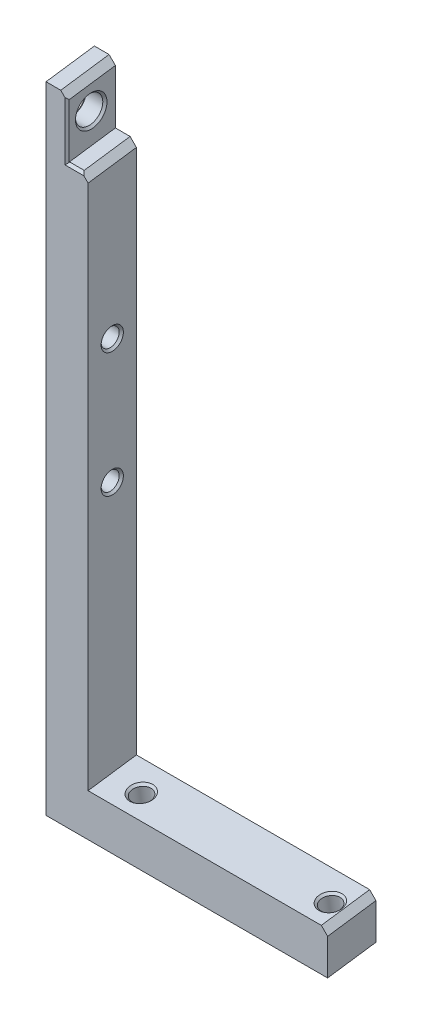
SolidWorks part; units mm, degrees
ref_plane "Top" through (0, 0, 0) normal (0, 0, 1) x (1, 0, 0)
ref_plane "Front" through (0, 0, 0) normal (0, 1, 0) x (1, 0, 0)
ref_plane "Right" through (0, 0, 0) normal (1, 0, 0) x (0, 0, -1)
sketch "Sketch4" plane through (0, 0, 0) normal (1, 0, 0) x (0, 0, -1)
  line L1 (0, 0) -> (11.5, 0)
  line L2 (0, 0) -> (0, 144)
  line L3 (0, 144) -> (11.5, 144)
  line L4 (11.5, 0) -> (11.5, 144)
  dimension "D1" = 11.5
  dimension "D2" = 144
extrude "Boss-Extrude2" add sketch "Sketch4" along normal blind 10
sketch "Sketch6" plane through (10, 0, 0) normal (1, 0, 0) x (0, 0, -1)
  line L0 (5.75, 0) -> (11.5, 0.8081)
  line L1 (0, 0) -> (11.5, 0) construction
  line L2 (11.5, 0) -> (11.5, 144) construction
  line L3 (11.5, 0.8081) -> (10.1083, 10.7108)
  line L4 (10.1083, 10.7108) -> (0.2056, 9.3191)
  line L5 (0.2056, 9.3191) -> (1.5973, -0.5836)
  line L6 (1.5973, -0.5836) -> (5.75, 0)
  line L7 (0, 144) -> (0, 0) construction
  dimension "D1" = 10
  dimension "D2" = 10
  dimension "D3" = 82
extrude "Boss-Extrude3" add sketch "Sketch6" along normal blind 57 and the other way blind 10
sketch "Sketch7" plane through (10, 0, 0) normal (1, 0, 0) x (0, 0, -1)
  line L0 (-3.1126, -1.2456) -> (11.8209, -3.029)
  line L2 (11.8209, -3.029) -> (11.8209, 0.8532)
  line L3 (11.8209, 0.8532) -> (-3.1126, -1.2456)
  line L4 (1.5973, -0.5836) -> (11.5, 0.8081) construction
extrude "Cut-Extrude2" cut sketch "Sketch7" against normal blind 10
sketch "Sketch8" plane through (0, 9.1102, 1.2804) normal (0, 0.9903, 0.1392) x (1, 0, 0)
  line L0 (10, 1.5005) -> (67, 1.5005) construction
  line L1 (67, 11.5005) -> (67, 1.5005) construction
  circle A0 centre (62.5, 6.5005) radius 2.25
  circle A1 centre (17.5, 6.5005) radius 2.25
  dimension "D2" = 4.5
  dimension "D3" = 4.5
  dimension "D1" = 45
  dimension "D4" = 5
  dimension "D5" = 4.5
extrude "Cut-Extrude3" cut sketch "Sketch8" against normal blind 10
sketch "Sketch11" plane through (0, 9.1102, 1.2804) normal (0, 0.9903, 0.1392) x (1, 0, 0)
  line L0 (13.5, 6.5005) -> (13.5, 0)
  line L1 (13.5, 0) -> (21.5, 0)
  line L3 (21.5, 0) -> (21.5, 6.5005)
  line L4 (10, 0) -> (0, 0) construction
  circle A0 centre (17.5, 6.5005) radius 4 construction
  arc A1 (21.5, 6.5005) -> (13.5, 6.5005) centre (17.5, 6.5005) ccw
  dimension "D1" = 8
sketch "Sketch12" plane through (67, 0, 0) normal (1, 0, 0) x (0, 0, -1)
  line L5 (0.2056, 9.3191) -> (10.1083, 10.7108) construction
  line L13 (1.5973, -0.5836) -> (0, -0.8081)
  line L14 (0, -0.8081) -> (0, 9.2902)
  line L16 (1.5973, -0.5836) -> (11.5, 0.8081) construction
  line L17 (0, 144) -> (0, 0) construction
  line L18 (11.5, 0.8081) -> (11.5, 10.9064)
  line L20 (11.5, 10.9064) -> (10.1083, 10.7108)
  line L21 (10.1083, 10.7108) -> (11.5, 0.8081)
  line L22 (10.1083, 10.7108) -> (0.2056, 9.3191) construction
  line L23 (11.5, 0.8081) -> (11.5, 144) construction
  line L25 (11.5, 0.8081) -> (10.1083, 10.7108) construction
  line L26 (0, 9.2902) -> (0.2056, 9.3191)
  line L27 (0.2056, 9.3191) -> (1.5973, -0.5836)
  line L28 (0.2056, 9.3191) -> (1.5973, -0.5836) construction
extrude "Boss-Extrude4" add sketch "Sketch12" against normal up to surface (67 mm away) up to face at (0, 48.0374, -4.3521)
sketch "Sketch13" plane through (10, 0, 0) normal (1, 0, 0) x (0, 0, -1)
  line L0 (11.5, 144) -> (11.5, 152)
  line L1 (11.5, 152) -> (0, 150.3838)
  line L2 (0, 150.3838) -> (0, 144)
  line L3 (0, 144) -> (11.5, 144)
  line L4 (11.5, 10.9064) -> (0, 9.2902) construction
  dimension "D1" = 8
extrude "Boss-Extrude5" add sketch "Sketch13" against normal blind 10
sketch "Sketch14" plane through (10, 0, 0) normal (1, 0, 0) x (0, 0, -1)
  line L0 (11.5, 10.9064) -> (11.5, 152) construction
  circle A0 centre (5.75, 144) radius 3.25
  dimension "D2" = 6.5
  dimension "D1" = 8
  dimension "D3" = 5.75
extrude "Cut-Extrude5" cut sketch "Sketch14" against normal blind 10
sketch "Sketch18" plane through (10, 0, 0) normal (1, 0, 0) x (0, 0, -1)
  line L0 (5.75, 99.6) -> (5.75, 70)
  line L1 (11.5, 10.9064) -> (11.5, 152) construction
  dimension "D1" = 5.75
  dimension "D2" = 29.6
  dimension "D3" = 70
hole_wizard "M4 Clearance Hole1" positions "Sketch19" profile "Sketch20" hole size "M4" standard "DIN" end condition through all
sketch "Sketch19" plane through (10, 0, 0) normal (1, 0, 0) x (0, 0, -1)
  point P0 (5.75, 70)
  point P3 (5.75, 99.6)
sketch "Sketch20" plane through (10, 70, -5.75) normal (0, 1, 0) x (0, 0, -1)
  line L0 (0, 0) -> (0, 10)
  line L1 (0, 10) -> (2.15, 10)
  line L2 (2.15, 10) -> (2.15, 0)
  line L5 (2.15, 0) -> (0, 0)
  line L11 (0, -6.35) -> (0, 107.95) construction
  dimension "Thru Hole Dia." = 4.3
  dimension "Thru Hole Depth" = 10
sketch "Sketch24" plane through (10, 0, 0) normal (1, 0, 0) x (0, 0, -1)
  line L0 (11.5, 152) -> (0, 150.3838)
  line L1 (0, 150.3838) -> (0, 136)
  line L2 (0, 150.3838) -> (0, 9.2902) construction
  line L3 (0, 136) -> (11.5, 137.6162)
  line L4 (11.5, 10.9064) -> (11.5, 152) construction
  line L5 (11.5, 137.6162) -> (11.5, 152)
  circle A0 centre (5.75, 144) radius 3.25 construction
  dimension "D1" = 8
extrude "Cut-Extrude7" cut sketch "Sketch24" against normal blind 5
chamfer "Chamfer2" distance 0.5 angle 45 10 edges at (10, 70, -7.9) (0, 70, -7.9) (10, 99.6, -7.9) (0, 99.6, -7.9) (0, 144, -9) (17.5, 9.7018, -2.9288) (17.5, -0.2009, -4.3206) (62.5, 9.7018, -2.9288) (62.5, -0.2009, -4.3206) (5, 144, -9)
chamfer "Chamfer5" distance 0.5 angle 45 2 edges at (7.5, 136, 0) (5, 143.1919, 0) first distance on face at (20.5, 73.7165, 0)
chamfer "Chamfer6" distance 1.5 angle 45 2 edges at (5, 151.227, -6) (10, 136.849, -6.0409)
chamfer "Chamfer7" distance 1.5 angle 45 1 edges at (67, 10.0983, -5.75)
